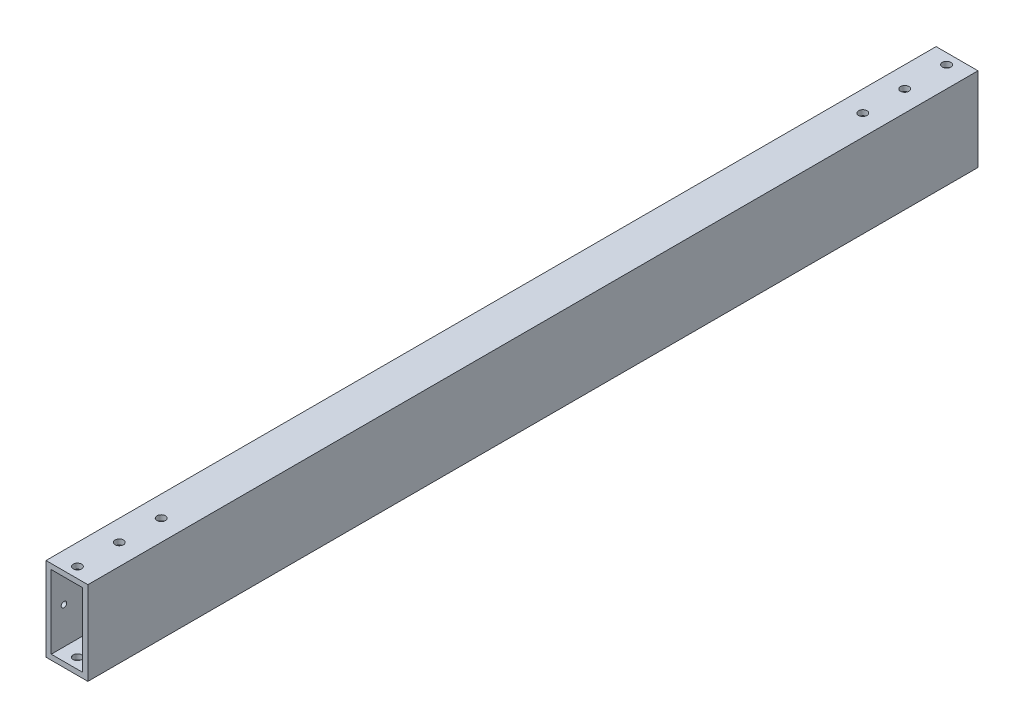
SolidWorks part; units mm, degrees
material "6061-T6 (SS)"
ref_plane "Front" through (0, 0, 0) normal (0, 0, 1) x (1, 0, 0)
ref_plane "Top" through (0, 0, 0) normal (0, 1, 0) x (1, 0, 0)
ref_plane "Right" through (0, 0, 0) normal (1, 0, 0) x (0, 0, -1)
sketch "Sketch1" plane through (0, 0, 0) normal (0, 0, 1) x (1, 0, 0)
  line L1 (-12.7, -25.4) -> (12.7, -25.4)
  line L2 (-12.7, -25.4) -> (-12.7, 25.4)
  line L3 (-12.7, 25.4) -> (12.7, 25.4)
  line L4 (12.7, -25.4) -> (12.7, 25.4)
  line L5 (-12.7, -25.4) -> (12.7, 25.4) construction
  line L6 (-12.7, 25.4) -> (12.7, -25.4) construction
  point P0 (0, 0)
  dimension "D1" = 25.4
  dimension "D2" = 50.8
extrude "Extrude-Thin1" add sketch "Sketch1" along normal blind 539.75 thin thin type one direction reverse wall 3.175
hole_wizard "#10 Clearance Hole1" positions "Sketch2" profile "Sketch3" hole size "#10" standard "ANSI Inch" end condition through all
sketch "Sketch2" plane through (0, 25.4, 0) normal (0, 1, 0) x (1, 0, 0)
  line L0 (-12.7, -539.75) -> (-12.7, 0) construction
  line L1 (12.7, -539.75) -> (-12.7, -539.75) construction
  point P0 (0, -533.4)
  point P2 (0, -508)
  point P4 (0, -482.6)
  point P6 (0, -6.35)
  point P8 (0, -31.75)
  point P10 (0, -57.15)
  dimension "D1" = 12.7
  dimension "D2" = 25.4
  dimension "D3" = 6.35
  dimension "D4" = 25.4
  dimension "D5" = 6.35
  dimension "D6" = 25.4
  dimension "D7" = 25.4
sketch "Sketch3" plane through (0, 25.4, 533.4) normal (1, 0, 0) x (0, 0, 1)
  line L0 (0, 0) -> (0, 50.8)
  line L1 (0, 50.8) -> (2.5527, 50.8)
  line L2 (2.5527, 50.8) -> (2.5527, 0)
  line L5 (2.5527, 0) -> (0, 0)
  line L11 (0, -6.35) -> (0, 107.95) construction
  dimension "Thru Hole Dia." = 5.1054
  dimension "Thru Hole Depth" = 50.8
sketch "Sketch6" plane through (-12.7, 0, 0) normal (-1, 0, 0) x (0, 0, 1)
  point P0 (172.05, 0)
  point P3 (112.05, 0)
  point P6 (52.05, 0)
  point P9 (232.05, 0)
  point P12 (292.05, 0)
  point P15 (352.05, 0)
  point P18 (412.05, 0)
  point P21 (472.05, 0)
  point P24 (532.05, 0)
hole_wizard "M4x0.7 Tapped Hole1" positions "Sketch6" profile "Sketch5" tap size "M4x0.7" standard "ANSI Metric" end condition up to next
cosmetic thread "Hole Thread1" parameters "D2"=4
cosmetic thread "Hole Thread2" parameters "D2"=4
cosmetic thread "Hole Thread3" parameters "D2"=4
cosmetic thread "Hole Thread4" parameters "D2"=4
cosmetic thread "Hole Thread5" parameters "D2"=4
cosmetic thread "Hole Thread6" parameters "D2"=4
cosmetic thread "Hole Thread7" parameters "D2"=4
cosmetic thread "Hole Thread8" parameters "D2"=4
cosmetic thread "Hole Thread9" parameters "D2"=4
sketch "Sketch5" plane through (-12.7, 0, 172.05) normal (0, 1, 0) x (0, 0, 1)
  line L0 (0, 0) -> (0, 3.175)
  line L1 (0, 3.175) -> (1.65, 3.175)
  line L2 (1.65, 3.175) -> (1.65, 0)
  line L5 (1.65, 0) -> (0, 0)
  line L11 (0, -6.35) -> (0, 107.95) construction
  dimension "Thru Tap Drill Dia." = 3.3
  dimension "Thru Tap Drill Depth" = 3.175
sketch "Sketch9" plane through (0, -25.4, 0) normal (0, -1, 0) x (-1, 0, 0)
  circle A1 centre (3.175, -298.958) radius 1.651 construction
  point P0 (3.175, -70.358)
  point P3 (-3.175, -95.758)
  point P6 (3.175, -127.508)
  point P9 (-3.175, -152.908)
  point P12 (3.175, -184.658)
  point P19 (3.175, -241.808)
  point P22 (-3.175, -267.208)
  point P25 (2.8902, -300.5843)
  point P29 (-3.175, -324.358)
  point P32 (3.175, -356.108)
  point P35 (-3.175, -381.508)
  point P38 (3.175, -413.258)
  point P41 (-3.175, -438.658)
  point P44 (3.175, -470.408)
  point P50 (-3.175, -210.058)
hole_wizard "1/8 (0.13) Diameter Hole1" positions "Sketch9" profile "Sketch8" hole size "1/8" standard "ANSI Inch" end condition up to next
sketch "Sketch8" plane through (-3.175, -25.4, 70.358) normal (1, 0, 0) x (0, 0, -1)
  line L0 (0, 0) -> (0, 3.175)
  line L1 (0, 3.175) -> (1.651, 3.175)
  line L2 (1.651, 3.175) -> (1.651, 0)
  line L5 (1.651, 0) -> (0, 0)
  line L11 (0, -6.35) -> (0, 107.95) construction
  dimension "Thru Hole Dia." = 3.302
  dimension "Thru Hole Depth" = 3.175
